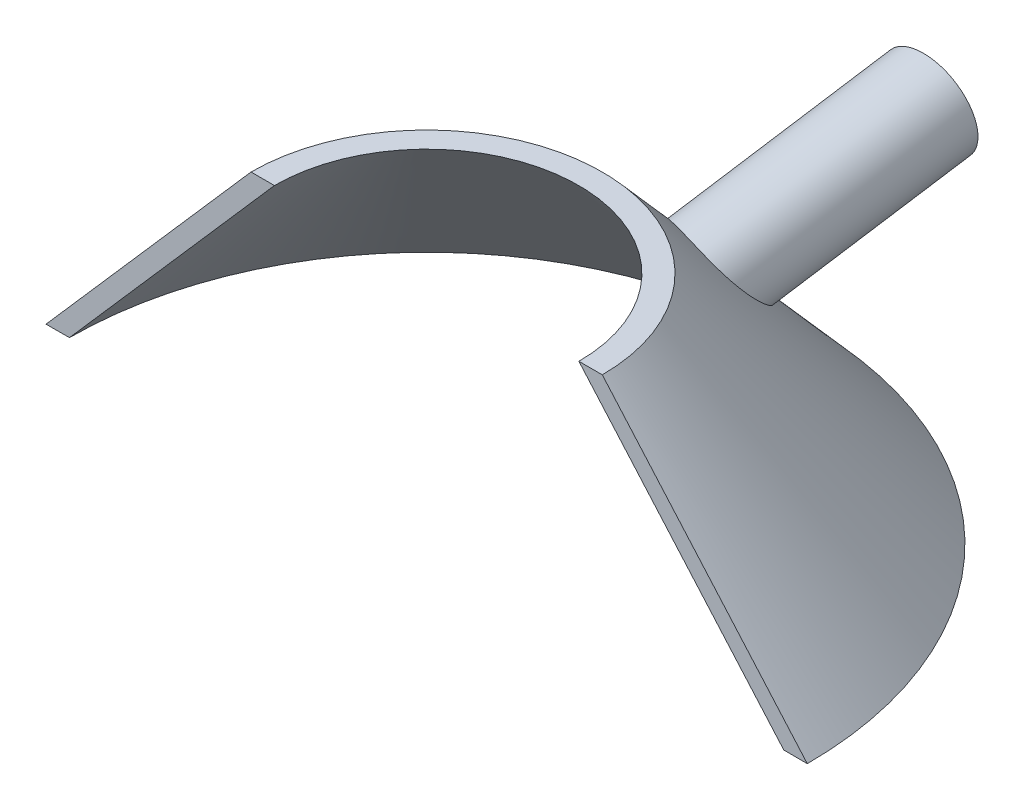
SolidWorks part; units mm, degrees
ref_plane "Front Plane" through (0, 0, 0) normal (0, 0, 1) x (1, 0, 0)
ref_plane "Top Plane" through (0, 0, 0) normal (0, 1, 0) x (1, 0, 0)
ref_plane "Right Plane" through (0, 0, 0) normal (1, 0, 0) x (0, 0, -1)
sketch "Sketch1" plane through (0, 0, 0) normal (0, 0, 1) x (1, 0, 0)
  line L0 (0, 40) -> (0, 0) construction
  line L1 (0, -55) -> (0, 55) construction
  line L2 (26, 40) -> (61, 0)
  line L3 (55, 0) -> (-55, 0) construction
  line L4 (26, 40) -> (30, 40)
  line L5 (30, 40) -> (65.0138, -0.0158)
  line L6 (65.0138, -0.0158) -> (61, 0)
  point P9 (86.101, 0)
  dimension "D1" = 40
  dimension "D2" = 26
  dimension "D3" = 61
  dimension "D4" = 4
revolve "Revolve1" add sketch "Sketch1" angle 180 about L0
ref_plane "Plane1" through (0, 32.2124, 36.8142) normal (0, 0.6585, 0.7526) x (1, 0, 0)
sketch "Sketch3" plane through (0, 32.2124, 36.8142) normal (0, 0.6585, 0.7526) x (1, 0, 0)
  circle A0 centre (0, -20.3521) radius 26
  point P2 (0, 0)
  point P3 (0, -20.3521)
  dimension "D1" = 52
extrude "Cut-Extrude1" cut sketch "Sketch3" against normal blind 10
mirror "Mirror1" about plane through (0, 0, 0) normal (0, 0, 1) of "Revolve1"
sketch "Sketch4" plane through (0, 32.2124, 36.8142) normal (0, 0.6585, 0.7526) x (1, 0, 0)
  line L0 (0, -20.3521) -> (-40.4283, -20.3521) construction
  line L1 (0, -20.3521) -> (33.3871, -20.3521) construction
  line L2 (0, -20.3521) -> (9.9485, -27.0624) construction
  arc A0 (14.8537, -41.6914) -> (-14.8537, -41.6914) centre (0, -20.3521) ccw construction
  arc A1 (14.8537, -41.6914) -> (-14.8537, -41.6914) centre (0, -20.3521) ccw
  point P3 (0, -20.3521)
  point P4 (9.9485, -27.0624)
  point P5 (9.9485, -27.0624)
  dimension "D1" = 146
  dimension "D2" = 12
ref_plane "Plane2" through (9.9485, 0, 0) normal (1, 0, 0) x (0, 0, -1)
sketch "Sketch5" plane through (9.9485, 0, 0) normal (1, 0, 0) x (0, 0, -1)
  line L0 (-54.6349, 11.8458) -> (64.8777, 11.8458) construction
  line L1 (-54.6349, 11.8458) -> (58.7864, 29.4916) construction
  point P6 (41.5423, 26.8088)
ref_plane "Plane3" through (9.9485, 26.8088, -41.5423) normal (0, 0.1537, -0.9881) x (-1, 0, 0)
sketch "Sketch6" plane through (9.9485, 26.8088, -41.5423) normal (0, 0.1537, -0.9881) x (-1, 0, 0)
  circle A0 centre (0, 0) radius 6.5
  circle A1 centre (0, 0) radius 8
  dimension "D1" = 13
  dimension "D2" = 16
extrude "Boss-Extrude2" add sketch "Sketch6" along normal blind 35 and the other way up to surface contours A1
extrude "Cut-Extrude8" cut sketch "Sketch6<6>" along normal blind 35 and the other way blind 10 contours A0
sketch "Sketch6<6>" plane through (9.9485, 26.8088, -41.5423) normal (0, 0.1537, -0.9881) x (-1, 0, 0) same geometry as "Sketch6"
sketch "Sketch7" plane through (0, 0, 0) normal (0, 0, 1) x (1, 0, 0)
  line L1 (-71.3061, 41.905) -> (93.5393, 41.905)
  line L2 (-71.3061, 41.905) -> (-71.3061, -10.8457)
  line L3 (-71.3061, -10.8457) -> (93.5393, -10.8457)
  line L4 (93.5393, 41.905) -> (93.5393, -10.8457)
extrude "Cut-Extrude9" cut sketch "Sketch7" along normal through all
